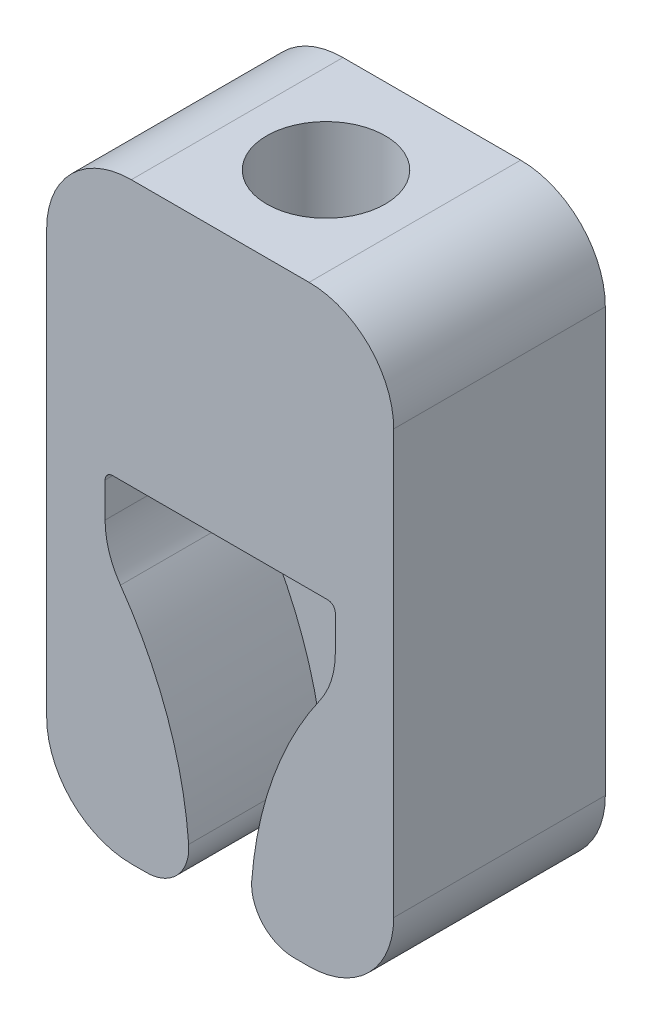
SolidWorks part; units mm, degrees
ref_plane "Front Plane" through (0, 0, 0) normal (0, 0, 1) x (1, 0, 0)
ref_plane "Top Plane" through (0, 0, 0) normal (0, 1, 0) x (1, 0, 0)
ref_plane "Right Plane" through (0, 0, 0) normal (1, 0, 0) x (0, 0, -1)
sketch "Sketch1" plane through (0, 0, 0) normal (0, 0, 1) x (1, 0, 0)
  line L1 (-20.5, 35) -> (20.5, 35)
  line L2 (-20.5, 35) -> (-20.5, -35)
  line L3 (-20.5, -35) -> (20.5, -35)
  line L4 (20.5, 35) -> (20.5, -35)
  line L5 (-20.5, 35) -> (20.5, -35) construction
  line L6 (-20.5, -35) -> (20.5, 35) construction
  point P0 (0, 0)
  dimension "D1" = 41
  dimension "16*4" = 70
extrude "Boss-Extrude1" add sketch "Sketch1" along normal blind 25
ref_plane "Plane1" through (0, 0, 12.5) normal (0, 0, 1) x (1, 0, 0)
sketch "Sketch6" plane through (0, 0, 25) normal (0, 0, 1) x (1, 0, 0)
  line L0 (-3.6, -35) -> (-3.6, -33)
  line L1 (-20.5, -35) -> (20.5, -35) construction
  line L3 (-13.6, -1.3772) -> (-13.6, 3.6228)
  line L4 (-13.6, 3.6228) -> (13.6, 3.6228)
  line L5 (13.6, 3.6228) -> (13.6, -1.3772)
  line L7 (3.6, -33) -> (3.6, -35)
  line L8 (3.6, -35) -> (-3.6, -35)
  line L9 (0, -35) -> (0, 3.6228) construction
  line L10 (-13.6, -1.3772) -> (0, -1.3772) construction
  line L11 (0, -1.3772) -> (13.6, -1.3772) construction
  line L12 (-11.7818, -7.1268) -> (0, -7.1268) construction
  line L13 (0, -7.1268) -> (11.7818, -7.1268) construction
  line L14 (-3.6, -33) -> (0, -33) construction
  line L15 (0, -33) -> (3.6, -33) construction
  line L16 (-11.7818, -7.1268) -> (-34.5966, 25.3392) construction
  arc A0 (13.6, -1.3772) -> (11.7818, -7.1268) centre (3.6, -1.3772) cw
  arc A1 (-11.7818, -7.1268) -> (-13.6, -1.3772) centre (-3.6, -1.3772) cw
  arc A2 (11.7818, -7.1268) -> (3.6, -33) centre (48.6, -33) ccw
  arc A3 (-3.6, -33) -> (-11.7818, -7.1268) centre (-48.6, -33) ccw
  dimension "D3" = 10
  dimension "D6" = 45
  dimension "D1" = 7.2
  dimension "D2" = 2
  dimension "D4" = 27.2
  dimension "D5" = 5
  dimension "D7" = 54.903
extrude "Cut-Extrude1" cut sketch "Sketch6" along direction (0, 0, 1) on the side against the normal offset from surface (16 mm away) 3.5 up to plane "Plane1" offset beyond the face yes
sketch "Sketch4" plane through (0, 35, 0) normal (0, 1, 0) x (1, 0, 0)
  line L0 (-20.5, 0) -> (20.5, -25) construction
  point P7 (0, -12.5)
hole_wizard "Tap Drill for M16x2.0 Tap1" positions "Sketch4" profile "Sketch3" hole size "M16x2.0" standard "ANSI Metric"
sketch "Sketch3" plane through (0, 35, 12.5) normal (1, 0, 0) x (0, 0, 1)
  line L0 (0, 0) -> (0, 28.5832)
  line L1 (0, 28.5832) -> (7, 24.3772)
  line L2 (7, 24.3772) -> (7, 0)
  line L5 (7, 0) -> (0, 0)
  line L10 (0, 28.5832) -> (-7, 24.3772) construction
  line L11 (0, -6.35) -> (0, 107.95) construction
  dimension "Hole Dia." = 14
  dimension "Hole Depth" = 24.3772
  dimension "Drill Angle" = 118
fillet "Fillet1" radius 10 4 edges at (20.5, 35, 12.5) (-20.5, 35, 12.5) (20.5, -35, 12.5) (-20.5, -35, 12.5)
fillet "Fillet2" radius 0.9 2 edges at (13.6, 3.6228, 17) (-13.6, 3.6228, 17)
fillet "Fillet4" radius 5 2 edges at (3.6, -35, 17) (-3.6, -35, 17)
